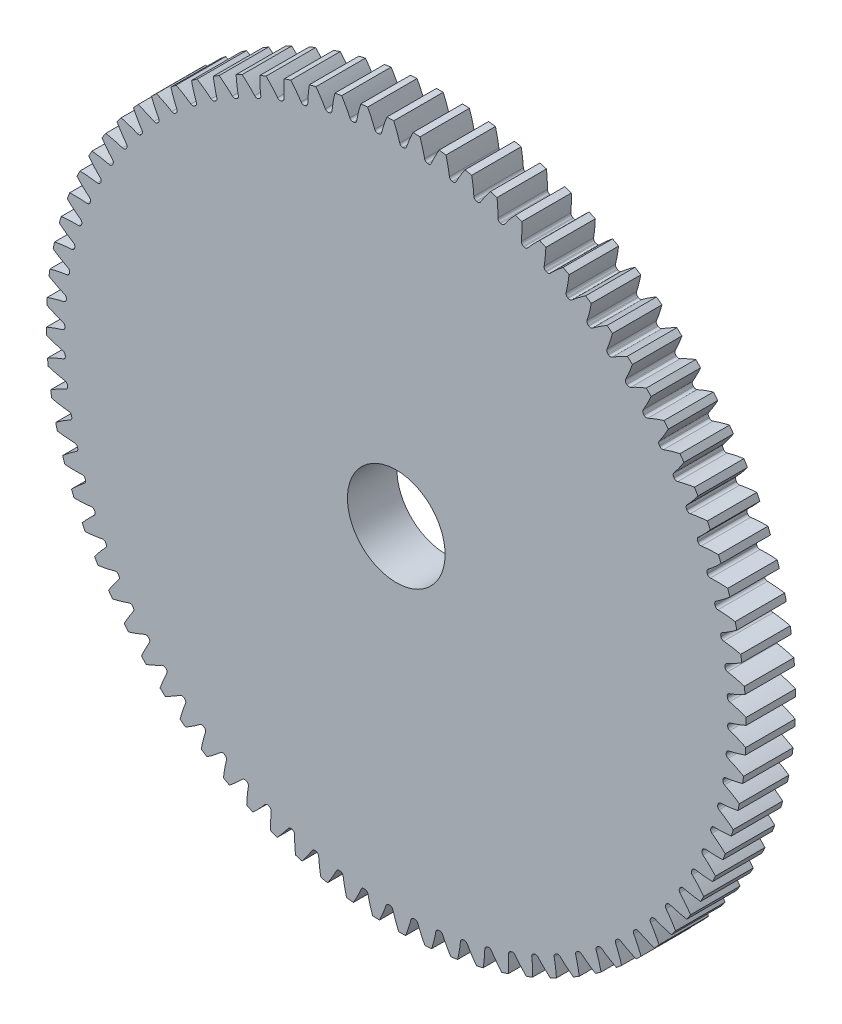
SolidWorks part; units mm, degrees
ref_plane "Front" through (0, 0, 0) normal (0, 0, 1) x (1, 0, 0)
ref_plane "Top" through (0, 0, 0) normal (0, 1, 0) x (1, 0, 0)
ref_plane "Right" through (0, 0, 0) normal (1, 0, 0) x (0, 0, -1)
sketch "Sketch3" plane through (0, 0, 0) normal (0, 0, 1) x (1, 0, 0)
  circle A0 centre (0, 0) radius 34.1313
  dimension "od" = 68.2625
extrude "gearBody" add sketch "Sketch3" along normal blind 4.826
sketch "Sketch2" plane through (0, 0, 0) normal (0, 0, 1) x (1, 0, 0)
  line L0 (0, 0) -> (28.9424, 11.9883) construction
  line L1 (39.3215, -6.3693) -> (0, 0) construction
  line L2 (0, 0) -> (36.3143, 0) construction
  line L3 (33.3374, -0.0752) -> (33.3125, -1.29) construction
  line L5 (33.325, -0.6826) -> (0, 0) construction
  line L7 (0, 0) -> (31.327, 0) construction
  arc A0 (31.3207, -0.6287) -> (31.3202, -0.6544) centre (0, 0) ccw construction
  arc A1 (34.1304, 0.2439) -> (34.0918, -1.6414) centre (0, 0) ccw construction
  arc A2 (33.3374, -0.0752) -> (33.3125, -1.29) centre (0, 0) ccw construction
  arc A3 (32.3265, -0.7041) -> (32.3282, -0.6203) centre (0, 0) ccw
  arc A4 (39.3215, -6.3693) -> (32.533, -0.9984) centre (28.4272, -13.1635) ccw
  arc A5 (39.3215, -6.3693) -> (39.5493, 4.7538) centre (0, 0) ccw
  arc A6 (39.5493, 4.7538) -> (32.5466, -0.3346) centre (28.9424, 11.9883) cw
  arc A7 (32.3282, -0.6203) -> (32.5466, -0.3346) centre (32.6319, -0.6261) cw
  arc A8 (32.533, -0.9984) -> (32.3265, -0.7041) centre (32.6302, -0.7107) cw
  point P6 (39.5493, 4.7538)
  point P22 (39.3215, -6.3693)
  dimension "baseDia" = 62.654
  dimension "od" = 68.2625
  dimension "pd" = 66.675
  dimension "rd" = 64.6684
  dimension "rFillet" = 0.3037
  dimension "pointX" = 39.5493
  dimension "pointY" = 4.7538
  dimension "CTT" = 1.2148
  dimension "flankCenterAngle" = 22.5
extrude "toothCut" cut sketch "Sketch2" along normal through all
pattern_circular "CirPattern1" count 84 over 360 about axis through (0, 0, 4.826) along (0, 0, -1) of "toothCut"
sketch "hub1Dia" plane through (0, 0, 0) normal (0, 0, -1) x (-1, 0, 0)
  circle A0 centre (0, 0) radius 12.7
  dimension "hub1Dia" = 25.4
sketch "hub2Dia" plane through (0, 0, 4.826) normal (0, 0, 1) x (1, 0, 0)
  circle A0 centre (0, 0) radius 12.7
  dimension "hub2dia" = 25.4
sketch "boreDia" plane through (0, 0, 0) normal (0, 0, 1) x (1, 0, 0)
  circle A0 centre (0, 0) radius 4.7625
  dimension "boreDia" = 9.525
extrude "bore" cut sketch "boreDia" against normal mid plane 25400
